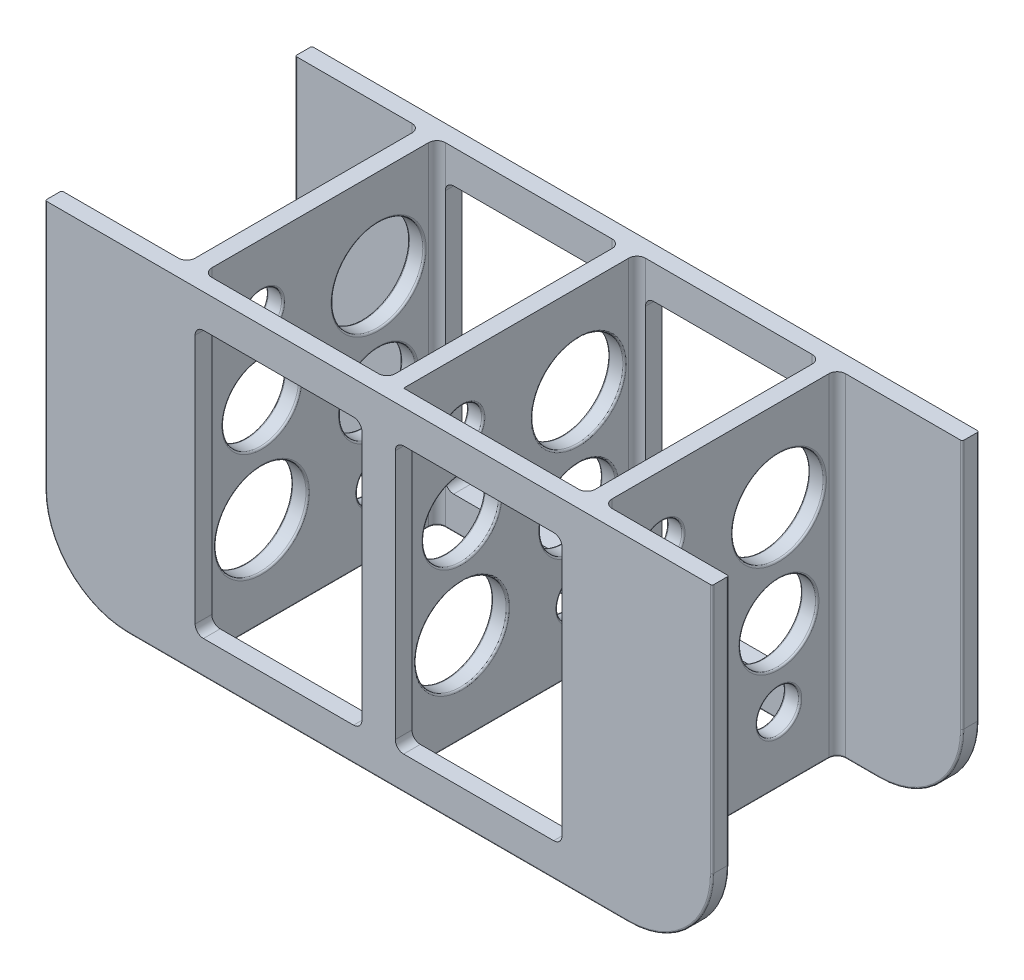
SolidWorks part; units mm, degrees
ref_plane "Ebene vorne" through (0, 0, 0) normal (0, 0, 1) x (1, 0, 0)
ref_plane "Ebene oben" through (0, 0, 0) normal (0, 1, 0) x (1, 0, 0)
ref_plane "Ebene rechts" through (0, 0, 0) normal (1, 0, 0) x (0, 0, -1)
sketch "Skizze1" plane through (0, 0, 0) normal (0, 1, 0) x (1, 0, 0)
  line L0 (-49.4615, 0) -> (54.3846, 0) construction
  line L1 (0, 32.3846) -> (0, -33.3846) construction
  line L2 (-1, -14) -> (-1, 14)
  line L3 (-23, -14) -> (-23, 14)
  line L4 (-25, -14) -> (-25, 14)
  line L5 (-23, 14) -> (-1, 14)
  line L6 (-23, -14) -> (-1, -14)
  line L7 (-25, 14) -> (-40, 14)
  line L8 (-40, 14) -> (-40, 16)
  line L9 (-40, 16) -> (40, 16)
  line L10 (-25, -14) -> (-40, -14)
  line L11 (-40, -14) -> (-40, -16)
  line L12 (-40, -16) -> (40, -16)
  line L13 (-25, -14) -> (-23, -14) construction
  line L14 (40, 14) -> (40, 16)
  line L15 (25, 14) -> (40, 14)
  line L16 (25, -14) -> (25, 14)
  line L17 (25, -14) -> (40, -14)
  line L18 (40, -14) -> (40, -16)
  line L19 (23, -14) -> (1, -14)
  line L20 (1, -14) -> (1, 14)
  line L21 (23, 14) -> (1, 14)
  line L22 (23, -14) -> (23, 14)
  point P9 (-23, 0)
  point P12 (-1, 0)
  point P14 (-25, 0)
  point P21 (0, 16)
  point P26 (0, -16)
  dimension "D1" = 2
  dimension "D2" = 1
  dimension "D3" = 40
  dimension "D4" = 15
  dimension "D5" = 32
extrude "Aufsatz-Linear austragen1" add sketch "Skizze1" along normal blind 40
sketch "Skizze2" plane through (-25, 0, 0) normal (-1, 0, 0) x (0, 0, 1)
  line L0 (0, 0) -> (0, 40) construction
  line L1 (-14, 0) -> (14, 0) construction
  line L2 (-14, 40) -> (14, 40) construction
  line L3 (-14, 20) -> (0, 20) construction
  line L6 (-14, 40) -> (-14, 0) construction
  line L7 (0, 20) -> (14, 20) construction
  line L8 (14, 40) -> (14, 0) construction
  line L9 (-7, 0) -> (-7, 40) construction
  line L10 (7, 0) -> (7, 40) construction
  line L11 (-7, 34.65) -> (-7, 5.35) construction
  circle A0 centre (-7, 29.15) radius 5.5
  circle A1 centre (-7, 17.05) radius 4.6
  circle A2 centre (-7, 7.9) radius 2.55
  circle A3 centre (7, 7.9) radius 2.55 construction
  circle A4 centre (7, 17.05) radius 4.6 construction
  circle A5 centre (7, 29.15) radius 5.5 construction
  circle A6 centre (7, 32.1) radius 2.55
  circle A7 centre (7, 22.95) radius 4.6
  circle A8 centre (7, 10.85) radius 5.5
  point P16 (-7, 20)
  point P19 (7, 20)
  point P26 (-7, 20)
  dimension "D1" = 11
  dimension "D2" = 9.2
  dimension "D3" = 5.1
  dimension "D4" = 12.1
  dimension "D5" = 9.15
extrude "Schnitt-Linear austragen1" cut sketch "Skizze2" against normal through all
sketch "Skizze3" plane through (0, 0, -14) normal (0, 0, 1) x (1, 0, 0)
  line L0 (-23, 20) -> (-1, 20) construction
  line L1 (-23, 40) -> (-23, 0) construction
  line L2 (-1, 40) -> (-1, 0) construction
  line L3 (1, 20) -> (23, 20) construction
  line L4 (1, 40) -> (1, 0) construction
  line L5 (23, 40) -> (23, 0) construction
  line L6 (-1, 40) -> (-23, 40) construction
  line L7 (-22, 4) -> (-2, 4)
  line L8 (-22, 4) -> (-22, 36)
  line L9 (-22, 36) -> (-2, 36)
  line L10 (-2, 4) -> (-2, 36)
  line L11 (-22, 4) -> (-2, 36) construction
  line L12 (-22, 36) -> (-2, 4) construction
  line L13 (2, 4) -> (22, 4)
  line L14 (2, 4) -> (2, 36)
  line L15 (2, 36) -> (22, 36)
  line L16 (22, 4) -> (22, 36)
  line L17 (2, 4) -> (22, 36) construction
  line L18 (2, 36) -> (22, 4) construction
  line L19 (-23, 23.65) -> (-23, 34.65) construction
  point P12 (-12, 20)
  point P17 (12, 20)
  dimension "D1" = 4
  dimension "D2" = 1
extrude "Schnitt-Linear austragen2" cut sketch "Skizze3" against normal through all both and the other way through all
fillet "Verrundung1" radius 10 4 edges at (40, 0, -15) (40, 0, 15) (-40, 0, 15) (-40, 0, -15)
fillet "Verrundung2" radius 1 11 edges at (25, 20, 14) (25, 20, -14) (1, 20, -14) (-23, 20, -14) (-23, 20, 14) (-25, 20, -14) (-25, 20, 14) (-1, 20, 14) (-1, 20, -14) (23, 20, -14) (23, 20, 14)
fillet "Verrundung3" radius 1 16 edges at (-2, 36, 15) (22, 4, 15) (22, 36, 15) (-22, 36, 15) (2, 36, 15) (2, 4, 15) (-22, 4, 15) (-2, 4, 15) (-2, 4, -15) (-22, 4, -15) (-22, 36, -15) (-2, 36, -15) (22, 4, -15) (2, 4, -15) (2, 36, -15) (22, 36, -15)
fillet "Verrundung4" radius 0.2 43 edges at (-40, 25, -14) (-37.0711, 2.9289, -14) (-40, 25, 14) (-37.0711, 2.9289, 14) (-40, 25, 16) (-37.0711, 2.9289, 16) (40, 25, 16) (37.0711, 2.9289, 16) (40, 25, 14) (37.0711, 2.9289, 14) (40, 25, -14) (37.0711, 2.9289, -14) (40, 25, -16) (37.0711, 2.9289, -16) (-40, 25, -16) (-37.0711, 2.9289, -16) (1, 0, 0.5) (1.2929, 0, -13.7071) (12, 0, -14) (22.7071, 0, -13.7071) (23, 0, 0) (22.7071, 0, 13.7071) (11.5, 0, 14) (-28, 0, -14) (-25.2929, 0, -13.7071) (-25, 0, 0) (-25.2929, 0, 13.7071) (-28, 0, 14) (0, 0, 16) (28, 0, 14) (25.2929, 0, 13.7071) (25, 0, 0) (25.2929, 0, -13.7071) (28, 0, -14) (0, 0, -16) (-1.2929, 0, 13.7071) (-12, 0, 14) (-22.7071, 0, 13.7071) (-23, 0, 0) (-22.7071, 0, -13.7071) (-12, 0, -14) (-1.2929, 0, -13.7071) (-1, 0, 0)
fillet "Verrundung5" radius 0.2 36 edges at (-25, 10.85, 12.5) (-23, 10.85, 1.5) (-25, 22.95, 11.6) (-23, 22.95, 2.4) (1, 10.85, 1.5) (-1, 10.85, 12.5) (1, 22.95, 2.4) (-1, 22.95, 11.6) (1, 32.1, 4.45) (-1, 32.1, 9.55) (-25, 32.1, 9.55) (-23, 32.1, 4.45) (-25, 29.15, -1.5) (-23, 29.15, -12.5) (-25, 17.05, -2.4) (-23, 17.05, -11.6) (1, 29.15, -12.5) (-1, 29.15, -1.5) (-25, 7.9, -4.45) (-23, 7.9, -9.55) (1, 17.05, -11.6) (-1, 17.05, -2.4) (1, 7.9, -9.55) (-1, 7.9, -4.45) (25, 29.15, -1.5) (23, 29.15, -1.5) (25, 7.9, -4.45) (23, 7.9, -4.45) (25, 10.85, 12.5) (23, 10.85, 12.5) (25, 17.05, -2.4) (23, 17.05, -2.4) (25, 22.95, 11.6) (23, 22.95, 11.6) (25, 32.1, 9.55) (23, 32.1, 9.55)
